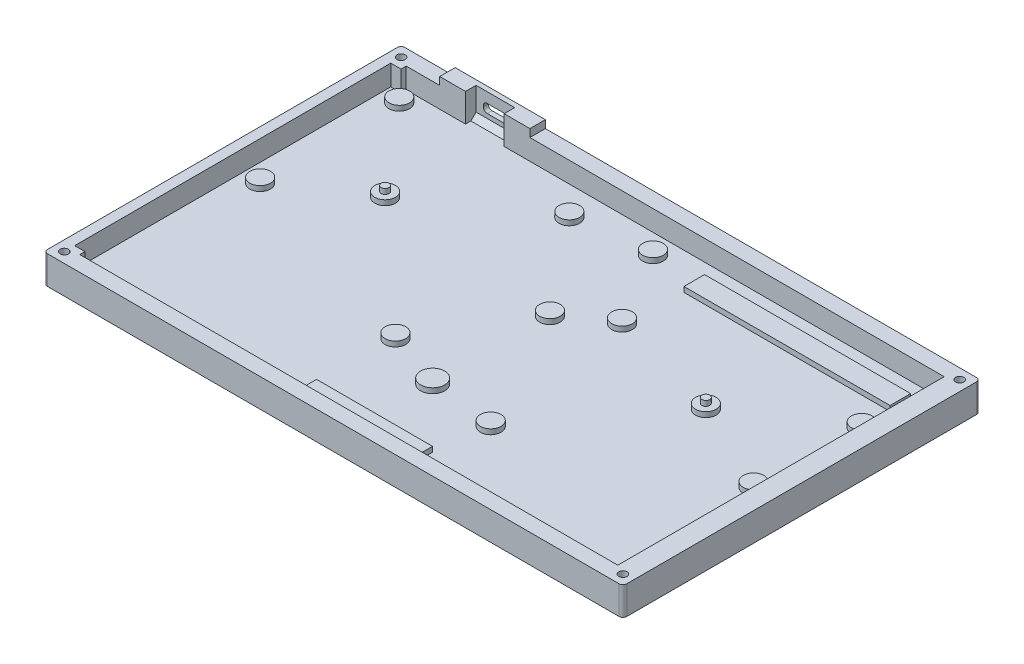
SolidWorks part; units mm, degrees
ref_plane "Front Plane" through (0, 0, 0) normal (0, 0, 1) x (1, 0, 0)
ref_plane "Top Plane" through (0, 0, 0) normal (0, 1, 0) x (1, 0, 0)
ref_plane "Right Plane" through (0, 0, 0) normal (1, 0, 0) x (0, 0, -1)
sketch "Sketch1" plane through (0, 0, 0) normal (0, 1, 0) x (1, 0, 0)
  line L1 (47.2637, 214.7949) -> (272.0716, 214.7949)
  line L2 (47.2637, 214.7949) -> (47.2637, 353.4944)
  line L3 (47.2637, 353.4944) -> (272.0716, 353.4944)
  line L4 (272.0716, 214.7949) -> (272.0716, 353.4944)
  line L6 (68.2637, 353.4944) -> (48.7637, 353.4944) construction
  line L7 (272.0716, 216.2949) -> (272.0716, 351.9944) construction
  line L8 (48.7637, 214.7949) -> (270.5716, 214.7949) construction
  line L9 (47.2637, 351.9944) -> (47.2637, 216.2949) construction
extrude "bottom_plate" add sketch "Sketch1" along normal blind 3
sketch "Sketch2" plane through (0, 3, 0) normal (0, 1, 0) x (1, 0, 0)
  line L9 (47.2637, 214.7949) -> (55.2637, 214.7949)
  line L10 (47.2637, 214.7949) -> (47.2637, 222.7949)
  line L11 (47.2637, 222.7949) -> (55.2637, 222.7949)
  line L12 (55.2637, 214.7949) -> (55.2637, 222.7949)
  line L13 (272.0716, 214.7949) -> (264.0716, 214.7949)
  line L14 (272.0716, 214.7949) -> (272.0716, 222.7949)
  line L15 (272.0716, 222.7949) -> (264.0716, 222.7949)
  line L16 (264.0716, 214.7949) -> (264.0716, 222.7949)
  line L17 (272.0716, 353.4944) -> (264.0716, 353.4944)
  line L18 (272.0716, 353.4944) -> (272.0716, 345.4944)
  line L19 (272.0716, 345.4944) -> (264.0716, 345.4944)
  line L20 (264.0716, 353.4944) -> (264.0716, 345.4944)
  line L21 (47.2637, 353.4944) -> (55.2637, 353.4944)
  line L22 (47.2637, 353.4944) -> (47.2637, 345.4944)
  line L23 (47.2637, 345.4944) -> (55.2637, 345.4944)
  line L24 (55.2637, 353.4944) -> (55.2637, 345.4944)
  dimension "D1" = 8
extrude "side_walls" add sketch "Sketch2" along normal blind 8
sketch "Sketch11" plane through (0, 3, 0) normal (0, 1, 0) x (1, 0, 0)
  line L0 (55.2637, 222.7949) -> (47.2637, 222.7949) construction
  line L1 (47.2637, 345.4944) -> (51.2637, 345.4944)
  line L2 (47.2637, 345.4944) -> (47.2637, 222.7949)
  line L3 (47.2637, 222.7949) -> (51.2637, 222.7949)
  line L4 (51.2637, 345.4944) -> (51.2637, 222.7949)
  line L5 (264.0716, 222.7949) -> (264.0716, 214.7949) construction
  line L6 (55.2637, 214.7949) -> (264.0716, 214.7949)
  line L7 (55.2637, 214.7949) -> (55.2637, 220.7949)
  line L8 (55.2637, 220.7949) -> (264.0716, 220.7949)
  line L9 (264.0716, 214.7949) -> (264.0716, 220.7949)
  line L10 (264.0716, 345.4944) -> (272.0716, 345.4944) construction
  line L11 (272.0716, 222.7949) -> (264.0716, 222.7949)
  line L12 (272.0716, 222.7949) -> (272.0716, 345.4944)
  line L13 (272.0716, 345.4944) -> (264.0716, 345.4944)
  line L14 (264.0716, 222.7949) -> (264.0716, 345.4944)
  line L15 (55.2637, 345.4944) -> (55.2637, 353.4944) construction
  line L16 (264.0716, 353.4944) -> (55.2637, 353.4944)
  line L17 (264.0716, 353.4944) -> (264.0716, 347.4944)
  line L18 (264.0716, 347.4944) -> (93.2637, 347.4944)
  line L19 (55.2637, 353.4944) -> (55.2637, 347.4944)
  line L20 (78.2637, 347.4944) -> (55.2637, 347.4944)
  line L22 (93.2637, 347.4944) -> (93.2637, 351.5944)
  line L23 (93.2637, 351.5944) -> (78.2637, 351.5944)
  line L24 (78.2637, 347.4944) -> (78.2637, 351.5944)
  point P32 (50.9923, 186.154)
  point P33 (66.2343, 186.4534)
  dimension "D1" = 8
  dimension "D2" = 6
  dimension "D3" = 6
  dimension "D4" = 4
  dimension "D5" = 4.1
  dimension "D6" = 31
  dimension "D7" = 15
extrude "usb_cutout" add sketch "Sketch11" along normal up to surface (8 mm away) up to face at (268.0716, 11, -218.7949)
hole_wizard "CSK for M3 SFHCS1" positions "Sketch5" profile "Sketch6" countersink size "M3" standard "ANSI Metric" end condition through all
sketch "Sketch5" plane through (0, 0, 0) normal (0, -1, 0) x (-1, 0, 0)
  point P29 (-51.2637, 218.7949)
  point P32 (-268.0716, 218.7949)
  point P35 (-268.0716, 349.4944)
  point P38 (-51.2637, 349.4944)
sketch "Sketch6" plane through (51.2637, 0, -218.7949) normal (1, 0, 0) x (0, 0, -1)
  line L0 (0, 0) -> (0, 11)
  line L1 (0, 11) -> (1.6, 11)
  line L2 (1.6, 11) -> (1.6, 1.76)
  line L3 (1.6, 1.76) -> (3.36, 0)
  line L5 (3.36, 0) -> (0, 0)
  line L6 (-1.6, 1.76) -> (-3.36, 0) construction
  line L11 (0, -6.35) -> (0, 107.95) construction
  dimension "Thru Hole Dia." = 3.2
  dimension "Thru Hole Depth" = 11
  dimension "Near C'Sink Dia." = 6.72
  dimension "Near C'Sink Angle" = 90
fillet "Fillet1" radius 1.5 4 edges at (47.2637, 5.5, -353.4944) (47.2637, 5.5, -214.7949) (272.0716, 5.5, -353.4944) (272.0716, 5.5, -214.7949)
sketch "Sketch14" plane through (0, 0, -351.5944) normal (0, 0, 1) x (1, 0, 0)
  line L0 (47.2637, 11) -> (47.2637, 0) construction
  line L9 (82.572, 6.6824) -> (88.7424, 6.6824)
  line L10 (81.072, 8.1824) -> (81.072, 8.5728)
  line L11 (82.572, 10.0728) -> (88.7424, 10.0728)
  line L12 (90.2424, 8.1824) -> (90.2424, 8.5728)
  line L13 (270.5716, 0) -> (48.7637, 0) construction
  arc A4 (81.072, 8.5728) -> (82.572, 10.0728) centre (82.572, 8.5728) cw
  arc A5 (82.572, 6.6824) -> (81.072, 8.1824) centre (82.572, 8.1824) cw
  arc A6 (88.7424, 6.6824) -> (90.2424, 8.1824) centre (88.7424, 8.1824) ccw
  arc A7 (88.7424, 10.0728) -> (90.2424, 8.5728) centre (88.7424, 8.5728) cw
  point P0 (81.072, 8.5728)
  dimension "D1" = 9.1705
  dimension "D5" = 1.5
  dimension "D2" = 3.3905
  dimension "D3" = 33.8083
  dimension "D4" = 6.6824
extrude "usb-c port" cut sketch "Sketch14" against normal blind 10
sketch "Sketch15" plane through (0, 11, 0) normal (0, 1, 0) x (1, 0, 0)
  line L0 (68.2637, 347.4944) -> (68.2637, 353.4944)
  line L1 (55.2637, 347.4944) -> (78.2637, 347.4944) construction
  line L2 (270.5716, 353.4944) -> (48.7637, 353.4944) construction
  line L3 (68.2637, 353.4944) -> (103.2637, 353.4944)
  line L4 (103.2637, 353.4944) -> (103.2637, 347.4944)
  line L5 (93.2637, 347.4944) -> (264.0716, 347.4944) construction
  line L6 (103.2637, 347.4944) -> (93.2637, 347.4944)
  line L7 (93.2637, 347.4944) -> (93.2637, 351.5944)
  line L8 (93.2637, 351.5944) -> (78.2637, 351.5944)
  line L9 (78.2637, 351.5944) -> (78.2637, 347.4944)
  line L10 (78.2637, 347.4944) -> (68.2637, 347.4944)
  dimension "D1" = 10
  dimension "D2" = 10
extrude "Boss-Extrude7" add sketch "Sketch15" along normal blind 3
chamfer "Chamfer1" distance 2 angle 45 1 edges at (85.7637, 3, -351.5944)
sketch "Sketch16" plane through (0, 3, 0) normal (0, 1, 0) x (1, 0, 0)
  line L0 (129.6676, 235.2949) -> (189.6676, 235.2949) construction
  line L1 (257.2346, 333.3169) -> (177.2346, 333.3169)
  line L2 (257.2346, 333.3169) -> (257.2346, 341.3169)
  line L3 (257.2346, 341.3169) -> (177.2346, 341.3169)
  line L4 (177.2346, 333.3169) -> (177.2346, 341.3169)
  line L7 (137.1676, 220.7949) -> (182.1676, 220.7949)
  line L8 (137.1676, 220.7949) -> (137.1676, 221.7949)
  line L9 (137.1676, 221.7949) -> (182.1676, 221.7949)
  line L10 (182.1676, 220.7949) -> (182.1676, 221.7949)
  line L11 (264.0716, 220.7949) -> (55.2637, 220.7949) construction
  line L13 (182.1676, 230.7949) -> (137.1676, 230.7949)
  line L14 (182.1676, 230.7949) -> (182.1676, 220.7949)
  line L15 (182.1676, 220.7949) -> (137.1676, 220.7949)
  line L16 (137.1676, 230.7949) -> (137.1676, 220.7949)
  circle A0 centre (58.2637, 341.7949) radius 4
  circle A1 centre (58.2637, 287.7949) radius 4
  circle A2 centre (136.7637, 261.7949) radius 4
  circle A4 centre (256.247, 281.3166) radius 4
  circle A5 centre (257.2346, 322.3169) radius 4
  circle A6 centre (159.2276, 299.3049) radius 4
  circle A7 centre (158.7276, 339.8049) radius 4
  circle A8 centre (129.7637, 336.2949) radius 4
  circle A9 centre (175.7381, 310.7923) radius 4
  circle A10 centre (220.7418, 298.3059) radius 4
  circle A11 centre (184.7562, 250.795) radius 4
  circle A12 centre (87.2637, 307.2949) radius 4
  arc A13 (142.1676, 247.7949) -> (142.1676, 222.7949) centre (142.1676, 235.2949) ccw construction
  arc A14 (177.1676, 222.7949) -> (177.1676, 247.7949) centre (177.1676, 235.2949) ccw construction
  circle A15 centre (159.2276, 253.8049) radius 4.6708
  circle A16 centre (159.6676, 235.2949) radius 2.1608 construction
  point P58 (159.6676, 235.2949)
  point P61 (141.4616, 122.4063)
  point P62 (0, 0)
  point P63 (159.6676, 230.7949)
  point P64 (0, 0)
  point P65 (160.1076, 253.8049)
  dimension "D1" = 8
  dimension "D2" = 1
  dimension "D3" = 10
  dimension "D4" = 45
  dimension "D5" = 8
  dimension "D8" = 80
  dimension "D9" = 11
extrude "pcb_support" add sketch "Sketch16" along normal blind 2 contours A0 | A12 | A1 | A7 | A8 | L4 L1 L2 L3 | A6 | A11 | A10 | A5 | A4 | L10 | A9 | A2 | L14 L13 L16 L15 | A15 region at (217.2346, 3, -337.3169) region at (159.6676, 3, -221.2949) region at (58.2637, 3, -341.7949) region at (58.2637, 3, -287.7949) region at (256.247, 3, -281.3166) region at (257.2346, 3, -322.3169) region at (159.2276, 3, -299.3049) region at (158.7276, 3, -339.8049) region at (129.7637, 3, -336.2949) region at (220.7418, 3, -298.3059) region at (184.7562, 3, -250.795) region at (87.2637, 3, -307.2949)
extrude "Boss-Extrude9" add sketch "Sketch16<3>" along normal blind 4 contours L10 region at (159.6676, 3, -221.2949)
sketch "Sketch16<3>" plane through (0, 3, 0) normal (0, 1, 0) x (1, 0, 0) same geometry as "Sketch16"
sketch "Sketch17" plane through (0, 5, 0) normal (0, 1, 0) x (1, 0, 0)
  circle A0 centre (87.2637, 307.2949) radius 1.5
  circle A1 centre (220.7418, 298.3059) radius 1.5
  dimension "D1" = 3
  dimension "D2" = 3
extrude "Boss-Extrude10" add sketch "Sketch17" along normal blind 2
